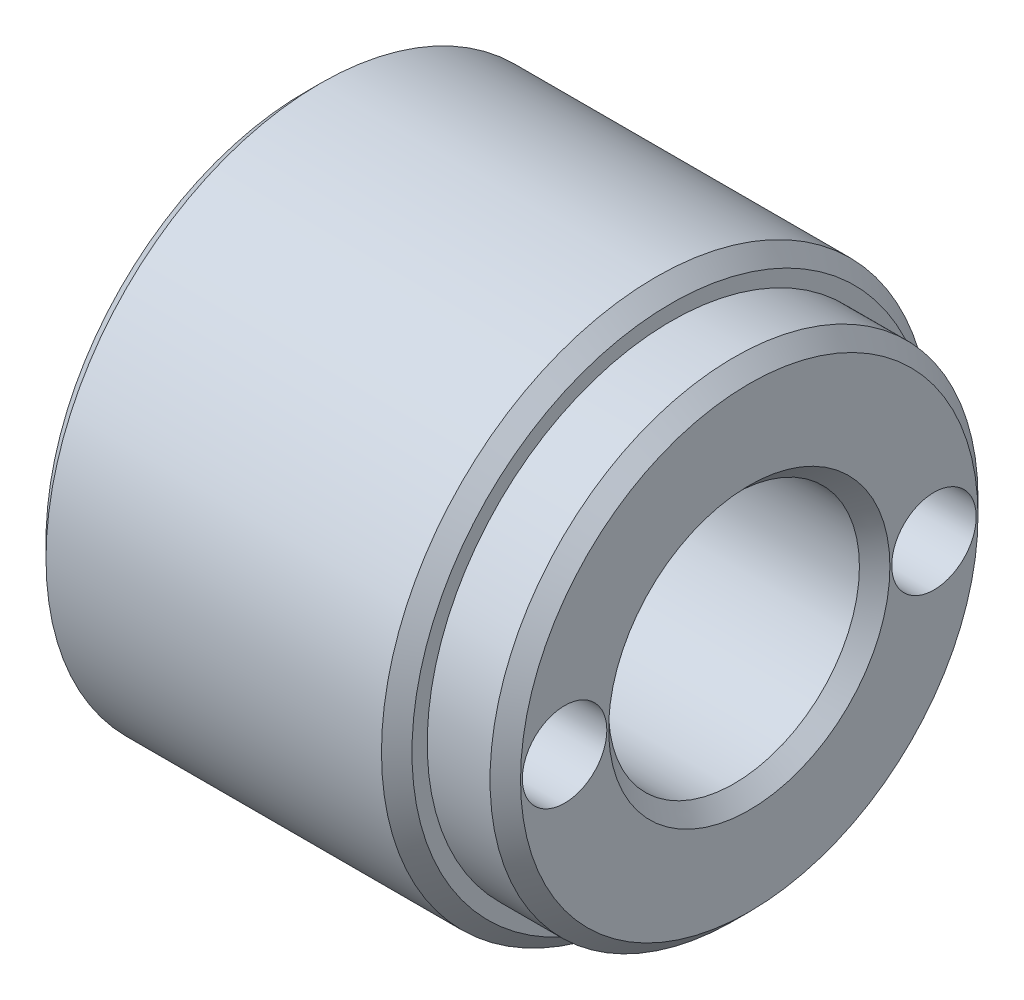
SolidWorks part; units mm, degrees
ref_plane "Front Plane" through (0, 0, 0) normal (0, 0, 1) x (1, 0, 0)
ref_plane "Top Plane" through (0, 0, 0) normal (0, 1, 0) x (1, 0, 0)
ref_plane "Right Plane" through (0, 0, 0) normal (1, 0, 0) x (0, 0, -1)
sketch "Sketch1" plane through (0, 0, 0) normal (1, 0, 0) x (0, 0, -1)
  line L0 (0, 0) -> (0, 0.7417) construction
  line L1 (-3.2639, 0) -> (-6.35, 0) construction
  circle A0 centre (0, 0) radius 6.35
  circle A1 centre (0, 0) radius 6.35
  circle A2 centre (0, 0) radius 3.2639
  circle A3 centre (-4.807, 0) radius 1.1
  circle A5 centre (0, 0) radius 7.1438
  circle A6 centre (4.807, 0) radius 1.1
  point P11 (-3.8362, 1.917)
  point P12 (-4.807, 0)
  dimension "D1" = 12.7
  dimension "D2" = 6.5278
  dimension "D3" = 2.2
  dimension "D4" = 14.2875
extrude "Inner Side Extrude" add sketch "Sketch1" along normal blind 2.032 contours A0 A2 A3 A6 region at (0, 0, 6.1704)
extrude "Outer Side Extrude" add sketch "Sketch1<3>" against normal blind 9.525 contours A0 A2 A3 A6 | A5 A0 region at (0, 0, 6.1704) region at (0, 0, 6.9417)
sketch "Sketch1<3>" plane through (0, 0, 0) normal (1, 0, 0) x (0, 0, -1) same geometry as "Sketch1"
chamfer "Chamfer so Steve Doesn't cut himself" distance 0.3969 angle 45 5 edges at (-9.525, 0, -3.2639) (2.032, 0, -3.2639) (2.032, 0, -6.35) (-9.525, 0, -7.1438) (0, 0, -7.1438)
